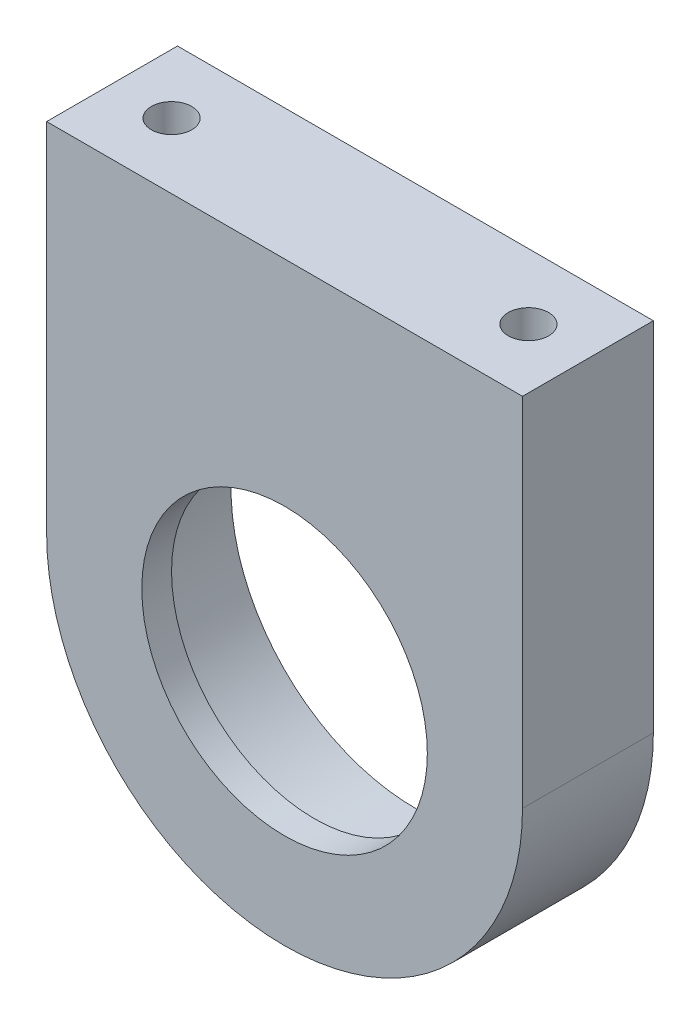
SolidWorks part; units mm, degrees
material "AISI 316 (1.4401)"
ref_plane "Płaszczyzna przednia" through (0, 0, 0) normal (0, 0, 1) x (1, 0, 0)
ref_plane "Płaszczyzna górna" through (0, 0, 0) normal (0, 1, 0) x (1, 0, 0)
ref_plane "Płaszczyzna prawa" through (0, 0, 0) normal (1, 0, 0) x (0, 0, -1)
sketch "Szkic1" plane through (0, 0, 0) normal (1, 0, 0) x (0, 0, -1)
  line L0 (0, 0) -> (26.9788, 0) construction
  line L1 (0, 24) -> (0, 40)
  line L2 (0, 40) -> (22, 40)
  line L3 (22, 40) -> (22, 31)
  line L4 (22, 31) -> (5, 31)
  line L5 (5, 31) -> (5, 24)
  line L6 (5, 24) -> (0, 24)
  dimension "D1" = 62
  dimension "D2" = 17
  dimension "D3" = 5
  dimension "D4" = 48
  dimension "D5" = 80
revolve "Obrót1" add sketch "Szkic1" angle 360 about L0
sketch "Szkic2" plane through (0, 0, -22) normal (0, 0, -1) x (-1, 0, 0)
  line L0 (-40, 0) -> (-40, 60)
  line L1 (-40, 60) -> (40, 60)
  line L2 (40, 60) -> (40, 0)
  circle A0 centre (0, 0) radius 40 construction
  arc A1 (40, 0) -> (-40, 0) centre (0, 0) ccw
  circle A2 centre (0, 0) radius 31 construction
  dimension "D1" = 60
extrude "Dodanie-wyciągnięcie1" add sketch "Szkic2" against normal up to surface (22 mm away) up to face at (24, 0, 0)
hole_wizard "Otwór gwintowany M81" positions "Szkic3" profile "Szkic4" tap size "M8" standard "DIN"
sketch "Szkic3" plane through (0, 60, 0) normal (0, 1, 0) x (1, 0, 0)
  line L0 (-40, 11) -> (-30, 11) construction
  line L1 (-40, 0) -> (-40, 22) construction
  line L2 (-30, 11) -> (30, 11) construction
  line L3 (30, 11) -> (40, 11) construction
  line L4 (40, 0) -> (40, 22) construction
  point P0 (-30, 11)
  point P2 (30, 11)
  dimension "D1" = 60
sketch "Szkic4" plane through (-30, 60, -11) normal (1, 0, 0) x (0, 0, 1)
  line L0 (0, 0) -> (0, 24.2929)
  line L1 (0, 24.2929) -> (3.4, 22.25)
  line L2 (3.4, 22.25) -> (3.4, 0)
  line L5 (3.4, 0) -> (0, 0)
  line L10 (0, 24.2929) -> (-3.4, 22.25) construction
  line L11 (0, -6.35) -> (0, 107.95) construction
  dimension "Średnica wiertła gwintu" = 6.8
  dimension "Głębokość otworu gwintowanego" = 22.25
  dimension "Kąt wiertła" = 118
cosmetic thread "Gwint otworu1" parameters "D1"=16, "D2"=8
cosmetic thread "Gwint otworu2" parameters "D1"=16, "D2"=8
